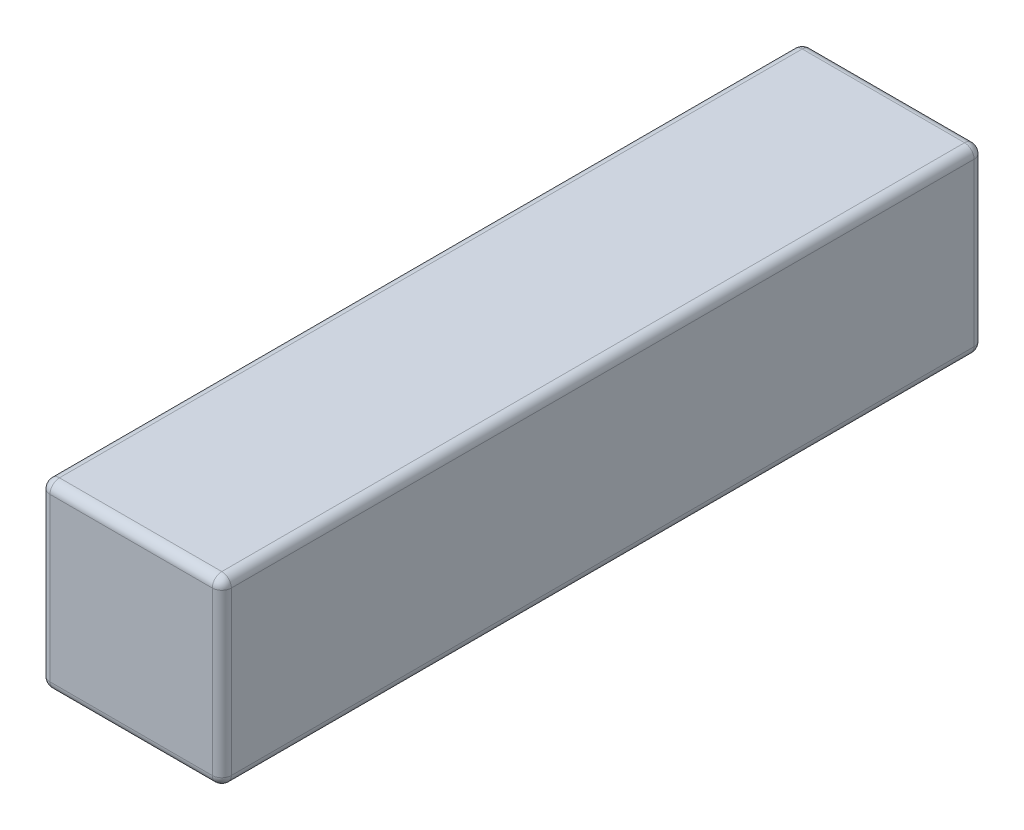
SolidWorks part; units mm, degrees
material "Plain Carbon Steel"
ref_plane "Front Plane" through (0, 0, 0) normal (0, 0, 1) x (1, 0, 0)
ref_plane "Top Plane" through (0, 0, 0) normal (0, 1, 0) x (1, 0, 0)
ref_plane "Right Plane" through (0, 0, 0) normal (1, 0, 0) x (0, 0, -1)
sketch "Sketch1" plane through (0, 0, 0) normal (0, 0, 1) x (1, 0, 0)
  line L1 (-4.7625, -4.7625) -> (4.7625, -4.7625)
  line L2 (-4.7625, -4.7625) -> (-4.7625, 4.7625)
  line L3 (-4.7625, 4.7625) -> (4.7625, 4.7625)
  line L4 (4.7625, -4.7625) -> (4.7625, 4.7625)
  line L5 (-4.7625, -4.7625) -> (4.7625, 4.7625) construction
  line L6 (-4.7625, 4.7625) -> (4.7625, -4.7625) construction
  dimension "D2" = 9.525
extrude "Boss-Extrude1" add sketch "Sketch1" along normal blind 40 contours L3 L4 L1 L2 region at (0, 0, 0)
fillet "Fillet1" radius 0.5 12 edges at (0, -4.7625, 40) (0, -4.7625, 0) (4.7625, -4.7625, 20) (4.7625, 0, 40) (4.7625, 0, 0) (-4.7625, 0, 40) (-4.7625, -4.7625, 20) (-4.7625, 0, 0) (4.7625, 4.7625, 20) (0, 4.7625, 40) (-4.7625, 4.7625, 20) (0, 4.7625, 0)
